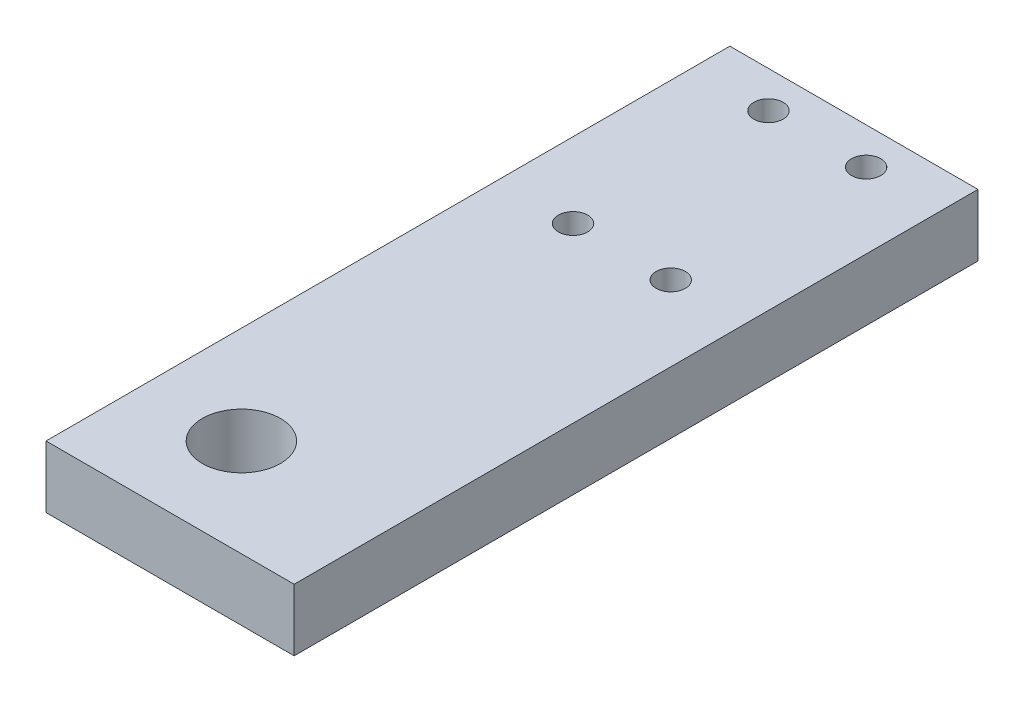
SolidWorks part; units mm, degrees
ref_plane "Front Plane" through (0, 0, 0) normal (0, 0, 1) x (1, 0, 0)
ref_plane "Top Plane" through (0, 0, 0) normal (0, 1, 0) x (1, 0, 0)
ref_plane "Right Plane" through (0, 0, 0) normal (1, 0, 0) x (0, 0, -1)
sketch "Sketch2" plane through (0, 0, 0) normal (0, 1, 0) x (1, 0, 0)
  line L1 (0, 0) -> (101.6, 0)
  line L2 (0, 0) -> (0, 280)
  line L3 (0, 280) -> (101.6, 280)
  line L4 (101.6, 0) -> (101.6, 280)
  dimension "D1" = 101.6
  dimension "D2" = 280
extrude "Boss-Extrude1" add sketch "Sketch2" along normal blind 25.4
sketch "Sketch3" plane through (0, 25.4, 0) normal (0, 1, 0) x (1, 0, 0)
  line L1 (0, 280) -> (50.8, 280)
  line L2 (0, 280) -> (0, 225)
  line L3 (0, 225) -> (50.8, 225)
  line L4 (50.8, 280) -> (50.8, 225)
  line L5 (30.8, 185) -> (70.8, 185)
  line L6 (30.8, 185) -> (30.8, 265)
  line L7 (30.8, 265) -> (70.8, 265)
  line L8 (70.8, 185) -> (70.8, 265)
  line L9 (30.8, 185) -> (70.8, 265) construction
  line L10 (30.8, 265) -> (70.8, 185) construction
  circle A0 centre (70.8, 265) radius 6
  circle A1 centre (30.8, 265) radius 6
  circle A2 centre (30.8, 185) radius 6
  circle A3 centre (70.8, 185) radius 6
  dimension "D1" = 50.8
  dimension "D2" = 55
  dimension "D3" = 40
  dimension "D4" = 80
extrude "Cut-Extrude1" cut sketch "Sketch3" against normal blind 25.4 contours A1 | A0 | A3 | A2
sketch "Sketch4" plane through (0, 25.4, 0) normal (0, 1, 0) x (1, 0, 0)
  line L1 (0, 280) -> (40, 280)
  line L2 (0, 280) -> (0, 40)
  line L3 (0, 40) -> (40, 40)
  line L4 (40, 280) -> (40, 40)
  circle A0 centre (40, 40) radius 16
  dimension "D1" = 240
  dimension "D2" = 40
extrude "Cut-Extrude2" cut sketch "Sketch4" against normal blind 25.4 contours A0
